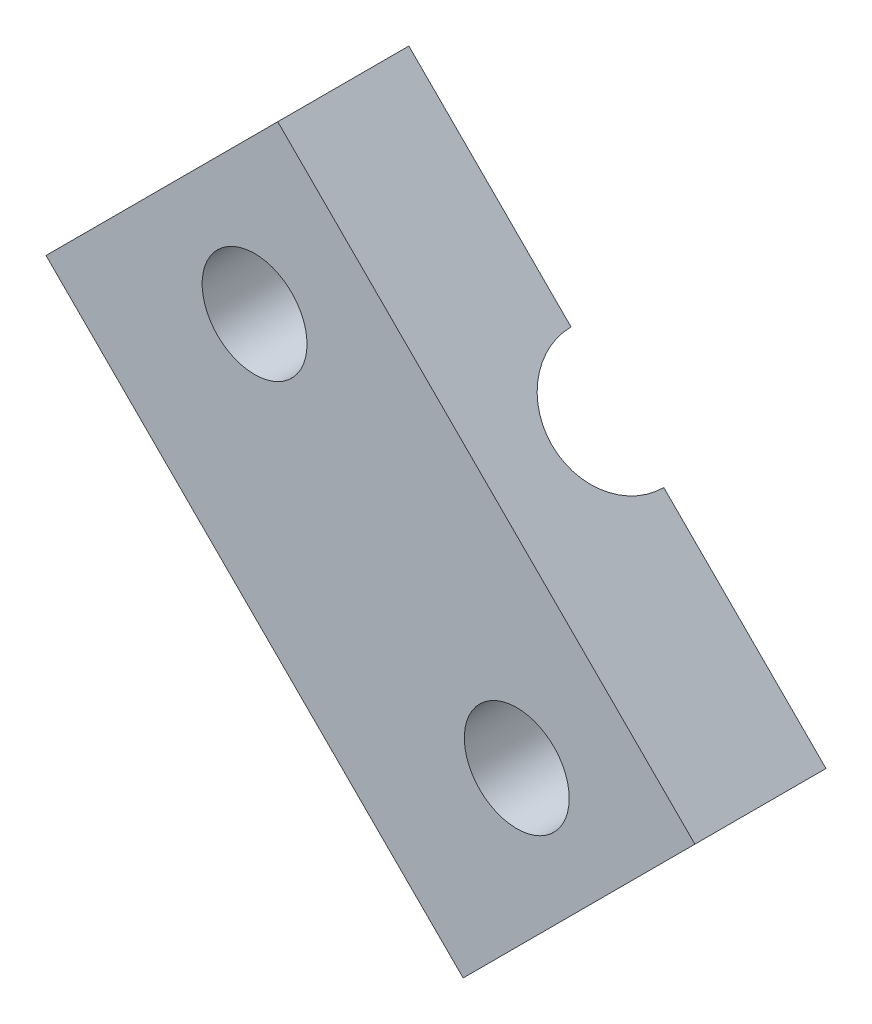
SolidWorks part; units mm, degrees
ref_plane "前视基准面" through (0, 0, 0) normal (0, 0, 1) x (1, 0, 0)
ref_plane "上视基准面" through (0, 0, 0) normal (0, 1, 0) x (1, 0, 0)
ref_plane "右视基准面" through (0, 0, 0) normal (1, 0, 0) x (0, 0, -1)
ref_axis "基准轴1" through (0, 0, 55) along (0, 0, -1)
ref_plane "基准面4" through (0, 0, 0) normal (0.7071, 0.7071, 0) x (0, 0, -1)
sketch "草图3" plane through (0, 0, 0) normal (0.7071, 0.7071, 0) x (0, 0, -1)
  line L0 (0, -9) -> (4, -9) construction
  line L1 (0, 9) -> (-4, 9)
  line L2 (0, 9) -> (0, -9)
  line L3 (0, -9) -> (-4, -9)
  line L4 (-4, 9) -> (-4, -9)
  circle A0 centre (0, 0) radius 2
  dimension "D1" = 0
  dimension "D2" = 4
extrude "凸台-拉伸1" add sketch "草图3" along normal blind 10 contours A0 L2 L1 L4 L3 region at (0, 0, 2.1101)
sketch "草图4" plane through (0, 0, 4) normal (0, 0, 1) x (1, 0, 0)
  circle A0 centre (0, 8) radius 1.6
  circle A1 centre (8, 0) radius 1.6
extrude "切除-拉伸1" cut sketch "草图4" against normal blind 10
